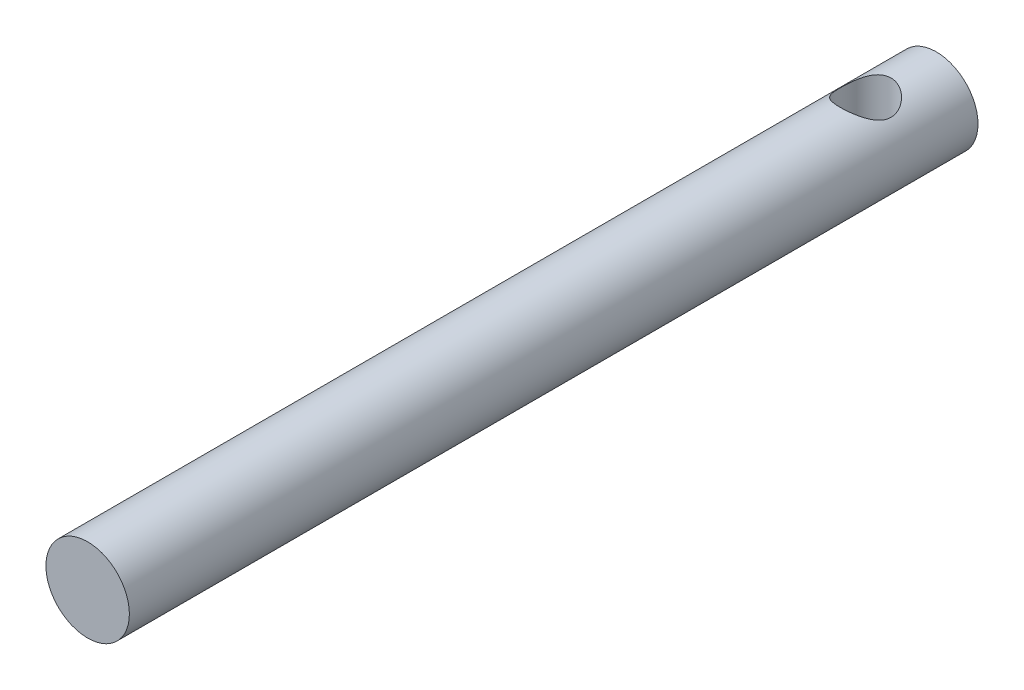
SolidWorks part; units mm, degrees
ref_plane "Front Plane" through (0, 0, 0) normal (0, 0, 1) x (1, 0, 0)
ref_plane "Top Plane" through (0, 0, 0) normal (0, 1, 0) x (1, 0, 0)
ref_plane "Right Plane" through (0, 0, 0) normal (1, 0, 0) x (0, 0, -1)
sketch "Sketch1" plane through (0, 0, 0) normal (0, 0, 1) x (1, 0, 0)
  circle A0 centre (0, 0) radius 1.475
  dimension "D1" = 2.95
extrude "Boss-Extrude1" add sketch "Sketch1" along normal blind 30
sketch "Sketch2" plane through (0, 0, 0) normal (0, 1, 0) x (1, 0, 0)
  line L0 (1.475, 0) -> (-1.475, 0) construction
  circle A0 centre (0, -2.5) radius 0.9
  dimension "D1" = 1.8
  dimension "D2" = 2.5
extrude "Cut-Extrude1" cut sketch "Sketch2" against normal blind 10 and the other way blind 10
